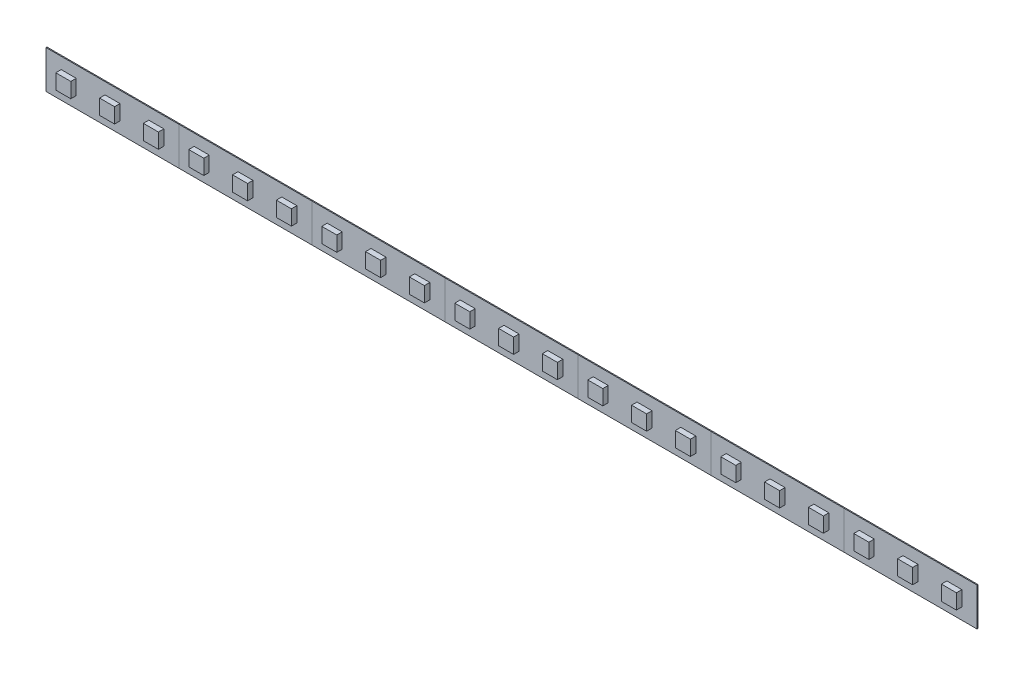
SolidWorks part; units mm, degrees
material "Epoxy, Unfilled"
ref_plane "Front Plane" through (0, 0, 0) normal (0, 0, 1) x (1, 0, 0)
ref_plane "Top Plane" through (0, 0, 0) normal (0, 1, 0) x (1, 0, 0)
ref_plane "Right Plane" through (0, 0, 0) normal (1, 0, 0) x (0, 0, -1)
sketch "Sketch1" plane through (0, 0, 0) normal (0, 0, 1) x (1, 0, 0)
  line L0 (-20.8, 0) -> (20.8, 0) construction
  line L1 (20.8, 5.955) -> (-20.8, 5.955)
  line L2 (20.8, 5.955) -> (20.8, -5.955)
  line L3 (20.8, -5.955) -> (-20.8, -5.955)
  line L4 (-20.8, 5.955) -> (-20.8, -5.955)
  line L5 (20.8, 5.955) -> (-20.8, -5.955) construction
  line L6 (20.8, -5.955) -> (-20.8, 5.955) construction
  line L7 (-2.35, 2.35) -> (2.35, 2.35)
  line L8 (-2.35, 2.35) -> (-2.35, -2.35)
  line L9 (-2.35, -2.35) -> (2.35, -2.35)
  line L10 (2.35, 2.35) -> (2.35, -2.35)
  line L11 (-2.35, 2.35) -> (2.35, -2.35) construction
  line L12 (-2.35, -2.35) -> (2.35, 2.35) construction
  line L13 (0, 0) -> (0, 5.955) construction
  line L18 (16.05, -2.35) -> (11.35, 2.35) construction
  line L19 (16.05, 2.35) -> (11.35, -2.35) construction
  line L20 (-16.05, 2.35) -> (-11.35, 2.35)
  line L21 (-16.05, 2.35) -> (-16.05, -2.35)
  line L22 (-16.05, -2.35) -> (-11.35, -2.35)
  line L23 (-11.35, 2.35) -> (-11.35, -2.35)
  line L24 (-16.05, 2.35) -> (-11.35, -2.35) construction
  line L25 (-16.05, -2.35) -> (-11.35, 2.35) construction
  line L26 (11.35, 2.35) -> (11.35, -2.35)
  line L27 (16.05, -2.35) -> (11.35, -2.35)
  line L28 (16.05, 2.35) -> (16.05, -2.35)
  line L29 (16.05, 2.35) -> (11.35, 2.35)
  point P0 (0, 0)
  point P6 (0, 0)
  point P18 (-13.7, 0)
  point P24 (13.7, 0)
  dimension "D1" = 41.6
  dimension "D2" = 11.91
  dimension "D3" = 13.7
  dimension "D5" = 9
extrude "Boss-Extrude1" add sketch "Sketch1" along normal blind 0.3 contours L1 L4 L3 L2 L29 L28 L27 L26 L7 L10 L9 L8 L20 L23 L22 L21 region at (20.3673, 0, 0)
extrude "Boss-Extrude2" add sketch "Sketch1<3>" along normal blind 2 contours L23 L20 L21 L22 | L10 L7 L8 L9 | L28 L29 L26 L27 region at (0, 0, 0) region at (-13.7, 0, 0) region at (13.7, 0, 0)
sketch "Sketch1<3>" plane through (0, 0, 0) normal (0, 0, 1) x (1, 0, 0) same geometry as "Sketch1"
pattern_linear "LPattern1" count 7 spacing 41.6 along (-1, 0, 0) of bodies 102
